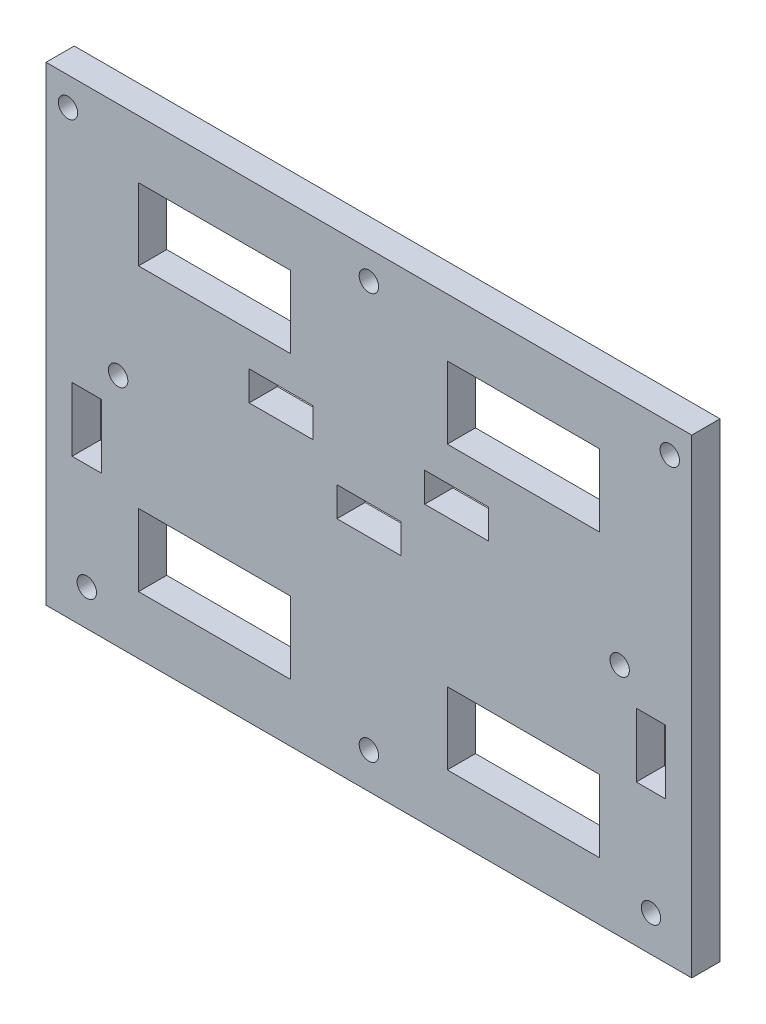
SolidWorks part; units mm, degrees
ref_plane "Front Plane" through (0, 0, 0) normal (0, 0, 1) x (1, 0, 0)
ref_plane "Top Plane" through (0, 0, 0) normal (0, 1, 0) x (1, 0, 0)
ref_plane "Right Plane" through (0, 0, 0) normal (1, 0, 0) x (0, 0, -1)
sketch "Sketch1" plane through (0, 0, 0) normal (0, 0, 1) x (1, 0, 0)
  line L0 (0, -37.5) -> (0, 37.5) construction
  line L1 (-51.5, -37.5) -> (51.5, -37.5)
  line L2 (-51.5, -37.5) -> (-51.5, 37.5)
  line L3 (-51.5, 37.5) -> (51.5, 37.5)
  line L4 (51.5, -37.5) -> (51.5, 37.5)
  line L5 (-51.5, -37.5) -> (51.5, 37.5) construction
  line L6 (-51.5, 37.5) -> (51.5, -37.5) construction
  line L7 (-51.5, 0) -> (51.5, 0) construction
  line L8 (-51.5, 22.5) -> (51.5, 22.5) construction
  line L9 (36.75, 16.75) -> (12.5, 28.25) construction
  line L10 (-36.75, 28.25) -> (-12.5, 28.25)
  line L11 (-36.75, 28.25) -> (-36.75, 16.75)
  line L12 (-36.75, 16.75) -> (-12.5, 16.75)
  line L13 (-12.5, 28.25) -> (-12.5, 16.75)
  line L14 (-36.75, 28.25) -> (-12.5, 16.75) construction
  line L15 (-36.75, 16.75) -> (-12.5, 28.25) construction
  line L16 (36.75, 28.25) -> (12.5, 16.75) construction
  line L17 (12.5, 28.25) -> (12.5, 16.75)
  line L18 (36.75, 16.75) -> (12.5, 16.75)
  line L19 (36.75, 28.25) -> (36.75, 16.75)
  line L20 (36.75, 28.25) -> (12.5, 28.25)
  line L21 (36.75, -28.25) -> (12.5, -16.75) construction
  line L22 (-36.75, -16.75) -> (-12.5, -28.25) construction
  line L23 (-36.75, -28.25) -> (-12.5, -16.75) construction
  line L24 (36.75, -16.75) -> (12.5, -28.25) construction
  line L25 (36.75, -28.25) -> (12.5, -28.25)
  line L26 (36.75, -28.25) -> (36.75, -16.75)
  line L27 (36.75, -16.75) -> (12.5, -16.75)
  line L28 (12.5, -28.25) -> (12.5, -16.75)
  line L29 (-12.5, -28.25) -> (-12.5, -16.75)
  line L30 (-36.75, -16.75) -> (-12.5, -16.75)
  line L31 (-36.75, -28.25) -> (-36.75, -16.75)
  line L32 (-36.75, -28.25) -> (-12.5, -28.25)
  point P0 (0, 0)
  point P12 (-24.625, 22.5)
  point P21 (24.625, 22.5)
  point P30 (24.625, -22.5)
  point P31 (-24.625, -22.5)
  dimension "D1" = 103
  dimension "D2" = 75
  dimension "D3" = 22.5
  dimension "D4" = 24.25
  dimension "D5" = 11.5
  dimension "D6" = 12.5
extrude "Boss-Extrude1" add sketch "Sketch1" along normal blind 4.5
sketch "Sketch2" plane through (0, 0, 4.5) normal (0, 0, 1) x (1, 0, 0)
  line L0 (0, -37.5) -> (0, 37.5) construction
  line L1 (-51.5, -37.5) -> (51.5, -37.5) construction
  line L2 (51.5, 37.5) -> (-51.5, 37.5) construction
  line L3 (-51.5, 0) -> (51.5, 0) construction
  line L4 (-51.5, 37.5) -> (-51.5, -37.5) construction
  line L5 (51.5, -37.5) -> (51.5, 37.5) construction
  line L6 (-40, 0) -> (40, 0) construction
  line L7 (-48, 33) -> (48, 33) construction
  circle A0 centre (-48, 33) radius 1.55
  circle A1 centre (48, 33) radius 1.55
  circle A2 centre (40, 0) radius 1.55
  circle A3 centre (-40, 0) radius 1.55
  circle A4 centre (0, 33) radius 1.55
  dimension "D1" = 3.1
  dimension "D7" = 3.1
  dimension "D8" = 3.1
  dimension "D9" = 3.1
  dimension "D2" = 48
  dimension "D3" = 33
  dimension "D4" = 80
  dimension "D5" = 40
  dimension "D6" = 0
extrude "screwHoles" cut sketch "Sketch2" against normal through all
sketch "Sketch3" plane through (0, 0, 4.5) normal (0, 0, 1) x (1, 0, 0)
  line L0 (-51.5, 9) -> (26.0486, 9) construction
  line L1 (-51.5, 37.5) -> (-51.5, -37.5) construction
  line L3 (0, 37.5) -> (0, -37.5) construction
  line L4 (51.5, 37.5) -> (-51.5, 37.5) construction
  line L5 (-51.5, -37.5) -> (51.5, -37.5) construction
  line L6 (19.1, 6.65) -> (8.9, 11.35) construction
  line L7 (-19.1, 11.35) -> (-8.9, 11.35)
  line L8 (-19.1, 11.35) -> (-19.1, 6.65)
  line L9 (-19.1, 6.65) -> (-8.9, 6.65)
  line L10 (-8.9, 11.35) -> (-8.9, 6.65)
  line L11 (-19.1, 11.35) -> (-8.9, 6.65) construction
  line L12 (-19.1, 6.65) -> (-8.9, 11.35) construction
  line L13 (19.1, 11.35) -> (8.9, 6.65) construction
  line L14 (8.9, 11.35) -> (8.9, 6.65)
  line L15 (19.1, 6.65) -> (8.9, 6.65)
  line L16 (19.1, 11.35) -> (19.1, 6.65)
  line L17 (19.1, 11.35) -> (8.9, 11.35)
  line L18 (-51.5, 37.5) -> (-51.5, -37.5) construction
  point P2 (-51.5, 0)
  point P12 (-14, 9)
  point P21 (14, 9)
  dimension "D1" = 10.2
  dimension "D2" = 4.7
  dimension "D3" = 14
  dimension "D4" = 9
extrude "BeltClamp" cut sketch "Sketch3" against normal through all
sketch "Sketch4" plane through (0, 0, 4.5) normal (0, 0, 1) x (1, 0, 0)
  line L0 (-51.5, 0) -> (51.5, 0) construction
  line L1 (-51.5, 37.5) -> (-51.5, -37.5) construction
  line L2 (51.5, -37.5) -> (51.5, 37.5) construction
  line L4 (-5.1, 2.35) -> (5.1, 2.35)
  line L5 (-5.1, 2.35) -> (-5.1, -2.35)
  line L6 (-5.1, -2.35) -> (5.1, -2.35)
  line L7 (5.1, 2.35) -> (5.1, -2.35)
  line L8 (-5.1, 2.35) -> (5.1, -2.35) construction
  line L9 (-5.1, -2.35) -> (5.1, 2.35) construction
  circle A0 centre (-40, 0) radius 1.55 construction
  point P6 (0, 0)
  dimension "D1" = 10.2
  dimension "D2" = 4.7
  dimension "D3" = 0
extrude "Cut-Extrude3" cut sketch "Sketch4" against normal through all
sketch "Sketch5" plane through (0, 0, 4.5) normal (0, 0, 1) x (1, 0, 0)
  line L0 (-51.5, -9.75) -> (51.5, -9.75) construction
  line L1 (-51.5, 37.5) -> (-51.5, -37.5) construction
  line L2 (51.5, -37.5) -> (51.5, 37.5) construction
  line L3 (5.1, -2.35) -> (5.1, 2.35) construction
  line L4 (0, -37.5) -> (0, 37.5) construction
  line L5 (-51.5, -37.5) -> (51.5, -37.5) construction
  line L6 (51.5, 37.5) -> (-51.5, 37.5) construction
  line L7 (-42.65, -14.85) -> (-47.35, -4.65) construction
  line L8 (42.65, -4.65) -> (47.35, -4.65)
  line L9 (42.65, -4.65) -> (42.65, -14.85)
  line L10 (42.65, -14.85) -> (47.35, -14.85)
  line L11 (47.35, -4.65) -> (47.35, -14.85)
  line L12 (42.65, -4.65) -> (47.35, -14.85) construction
  line L13 (42.65, -14.85) -> (47.35, -4.65) construction
  line L14 (-42.65, -4.65) -> (-47.35, -14.85) construction
  line L15 (-47.35, -4.65) -> (-47.35, -14.85)
  line L16 (-42.65, -14.85) -> (-47.35, -14.85)
  line L17 (-42.65, -4.65) -> (-42.65, -14.85)
  line L18 (-42.65, -4.65) -> (-47.35, -4.65)
  line L19 (45, -9.75) -> (45, -37.5) construction
  line L20 (-45, -9.75) -> (-45, -37.5) construction
  line L21 (-45, -31.75) -> (45, -31.75) construction
  circle A0 centre (45, -31.75) radius 1.55
  circle A1 centre (-45, -31.75) radius 1.55
  circle A2 centre (0, -31.75) radius 1.55
  point P6 (5.1, 0)
  point P15 (45, -9.75)
  point P24 (-45, -9.75)
  dimension "D7" = 3.1
  dimension "D5" = 3.1
  dimension "D1" = 9.75
  dimension "D2" = 10.2
  dimension "D3" = 4.7
  dimension "D4" = 45
  dimension "D6" = 22
extrude "Cut-Extrude4" cut sketch "Sketch5" against normal through all
sketch "Sketch6" plane through (0, 0, 4.5) normal (0, 0, 1) x (1, 0, 0)
  line L0 (-47.35, -9.75) -> (47.35, -9.75) construction
  line L1 (-47.35, -4.65) -> (-47.35, -14.85) construction
  line L2 (47.35, -14.85) -> (47.35, -4.65) construction
  line L3 (0, -2.35) -> (0, -37.5) construction
  line L4 (-5.1, -2.35) -> (5.1, -2.35) construction
  line L5 (-51.5, -37.5) -> (51.5, -37.5) construction
  line L6 (45, -14.85) -> (45, -4.65) construction
  line L7 (42.65, -14.85) -> (47.35, -14.85) construction
  line L8 (47.35, -4.65) -> (42.65, -4.65) construction
  line L9 (42.65, -4.65) -> (42.65, -14.85) construction
  line L10 (41.65, -15.85) -> (48.35, -15.85)
  line L11 (41.65, -15.85) -> (41.65, -3.65)
  line L12 (41.65, -3.65) -> (48.35, -3.65)
  line L13 (48.35, -15.85) -> (48.35, -3.65)
  line L14 (41.65, -15.85) -> (48.35, -3.65) construction
  line L15 (41.65, -3.65) -> (48.35, -15.85) construction
  line L16 (-41.65, -3.65) -> (-48.35, -15.85) construction
  line L17 (-41.65, -15.85) -> (-48.35, -3.65) construction
  line L18 (-45, -14.85) -> (-45, -4.65) construction
  line L19 (-48.35, -15.85) -> (-48.35, -3.65)
  line L20 (-41.65, -3.65) -> (-48.35, -3.65)
  line L21 (-41.65, -15.85) -> (-41.65, -3.65)
  line L22 (-41.65, -15.85) -> (-48.35, -15.85)
  circle A0 centre (45, -9.75) radius 1.55
  circle A1 centre (-45, -9.75) radius 1.55
  point P18 (45, -9.75)
  dimension "D3" = 3.1
  dimension "D1" = 1
  dimension "D2" = 1
extrude "FrontToRear1" [suppressed] add sketch "Sketch6" against normal up to surface (4.5 mm away) up to face at (1.55, -31.75, 0)
sketch "Sketch7" plane through (0, 0, 4.5) normal (0, 0, 1) x (1, 0, 0)
  line L0 (5.1, 2.35) -> (-5.1, 2.35) construction
  line L1 (-45, -3.35) -> (45, -3.35)
  line L2 (-45, -3.35) -> (-45, 3.35)
  line L3 (-45, 3.35) -> (45, 3.35)
  line L4 (45, -3.35) -> (45, 3.35)
  line L5 (-45, -3.35) -> (45, 3.35) construction
  line L6 (-45, 3.35) -> (45, -3.35) construction
  circle A0 centre (40, 0) radius 1.55 construction
  point P0 (0, 0)
  dimension "D1" = 1
  dimension "D2" = 5
extrude "FrontToRear2" [suppressed] add sketch "Sketch7" against normal through all
equation "\"X-ROD-SPACING\"=45"
equation "\"Y-ROD-SPACING\"=75"
equation "\"Z-ROD-SPACING\"=17.5"
equation "\"Y-BED-OFFSET\"=2"
equation "\"Y-BED-ROD-INSET\"=3.5"
equation "\"Y-BED-SCREW-SPACING\"=209"
equation "\"Y-BED-SCREW-CUTOUT-SLOT-HEIGHT\"=2"
equation "\"T-SLOT-NUT-FILLET-RADIUS\"=0.25"
equation "\"T-SLOT-SCREW-SHAFT-RADIUS\"=1.75"
equation "\"T-SLOT-SCREW-SHAFT-CUTOUT-LENGTH\"=10.5"
equation "\"T-SLOT-NUT-DEPTH\"=4.2"
equation "\"T-SLOT-NUT-WIDTH\"=3"
equation "\"T-SLOT-NUT-END-DISTANCE\"=8"
equation "\"ACRYLIC-THICKNESS\"=10"
equation "\"ACRYLIC-THICKNESS2\"=4.5"
equation "\"ACRYLIC-TAB-CUTOUT-SIZE\"=\"ACRYLIC-THICKNESS\"+\"ACRYLIC-TAB-TOLERANCE\"*2"
equation "\"ACRYLIC-TAB-WIDTH\"=\"ACRYLIC-THICKNESS\""
equation "\"ACRYLIC-M3-HOLE\"=3.1"
equation "\"SMOOTHROD-CAP-SCREW-DISTANCE\"=20"
equation "\"FRAME-WIDTH-INNER\"=370"
equation "\"NEMA17-HOLE-SPACING\"=31"
equation "\"NEMA17-CENTRAL-CUTOUT\"=22.5"
equation "\"Z-BRACKET-REACH\"=55"
equation "\"Z-ROD-INSET\"=16"
equation "\"TOP-BRACKET-SPACING\"=40"
equation "\"SMOOTHROD-X-LENGTH\"=350"
equation "\"SMOOTHROD-Y-LENGTH\"=350"
equation "\"SMOOTHROD-Z-LENGTH\"=350"
equation "\"SMOOTHROD-TIGHTENING-HEADROOM\"=.25"
equation "\"LEADSCREW-Z-LENGTH\"=300"
equation "\"SCREW-LENGTH-FRAME\"=\"ACRYLIC-THICKNESS\" + 10"
equation "\"SCREW-LENGTH-MOTOR\"=\"ACRYLIC-THICKNESS\" + 5"
equation "\"SCREW-HEAD-RADIUS\"=6"
equation "\"PRINTED-X-SMOOTHROD-DIAMETER\"=8.2"
equation "\"PRINTED-X-SMOOTHROD-CUTOUT\"=10"
equation "\"PRINTED-X-BASE-HEIGHT\"=10"
equation "\"PRINTED-LM8UU-CUTOUT-SIZE\"=15.25"
equation "\"PRINTED-LM8UU-CUTOUT-LENGTH\"=24.5"
equation "\"PRINTED-X-IDLER-HEIGHT\"=16"
equation "\"PSU-MOUNTING-WIDTH\"=95"
equation "\"PSU-MOUNTING-HEIGHT\"=177"
equation "\"Y-BELT-TO-ROD-DISTANCE\"=20"
equation "\"SPOOL-HOLDER-ROD-SPACING\"=150"
equation "\"D3@Sketch1\"=\"X-ROD-SPACING\"/2"
equation "\"D4@Sketch1\"=\"ACRYLIC-X-CARRIAGE-LM8UU-CUTOUT-WIDTH\""
equation "\"D1@Boss-Extrude1\"=\"ACRYLIC-THICKNESS2\""
equation "\"D1@Sketch2\"=\"ACRYLIC-M3-HOLE\""
equation "\"D1@Sketch3\"=\"ACRYLIC-TAB-CUTOUT-SIZE\""
equation "\"D2@Sketch3\"=\"ACRYLIC-THICKNESS2\"+\"ACRYLIC-TAB-TOLERANCE\"*2"
equation "\"ACRYLIC-X-CARRIAGE-WIDTH\"=55"
equation "\"ACRYLIC-X-CARRIAGE-HEIGHT\"=75"
equation "\"D2@Sketch1\"=\"ACRYLIC-X-CARRIAGE-HEIGHT\""
equation "\"ACRYLIC-X-CARRIAGE-CENTER-TAB-SPACING\"=14"
equation "\"D3@Sketch3\"=\"ACRYLIC-X-CARRIAGE-CENTER-TAB-SPACING\""
equation "\"SCREW-LENGTH-EXTRUDER\"=28"
equation "\"ACRYLIC-X-CARRIAGE-SCREW-SPACING-X\"=15"
equation "\"ACRYLIC-X-CARRIAGE-SCREW-SPACING-Y\"=33"
equation "\"D3@Sketch2\"=\"ACRYLIC-X-CARRIAGE-SCREW-SPACING-Y\""
equation "\"D1@Sketch4\"=\"ACRYLIC-TAB-CUTOUT-SIZE\""
equation "\"D2@Sketch4\"=\"ACRYLIC-THICKNESS2\"+\"ACRYLIC-TAB-TOLERANCE\"*2"
equation "\"D2@Sketch5\"=\"ACRYLIC-TAB-CUTOUT-SIZE\""
equation "\"D3@Sketch5\"=\"ACRYLIC-THICKNESS2\"+\"ACRYLIC-TAB-TOLERANCE\"*2"
equation "\"ACRYLIC-X-CARRIAGE-EXTRUDER-SHELF-DEPTH\"=\"ACRYLIC-X-CARRIAGE-EXTRUDER-OFFSET\" + 28"
equation "\"ACRYLIC-X-CARRIAGE-EXTRUDER-BRACE-SPACING\"=23"
equation "\"D4@Sketch5\"=\"ACRYLIC-X-CARRIAGE-DUAL-MOUNT-BRACE-WIDTH\""
equation "\"D1@Sketch5\"=\"ACRYLIC-THICKNESS2\"/2 + 7.5"
equation "\"D4@Sketch2\"=\"ACRYLIC-X-CARRIAGE-DUAL-MOUNT-SCREW-WIDTH\"*2"
equation "\"D5@Sketch2\"=\"ACRYLIC-X-CARRIAGE-DUAL-MOUNT-SCREW-WIDTH\""
equation "\"D7@Sketch2\"=\"ACRYLIC-M3-HOLE\""
equation "\"D8@Sketch2\"=\"ACRYLIC-M3-HOLE\""
equation "\"ACRYLIC-X-CARRIAGE-LM8UU-CUTOUT-WIDTH\"=24.25"
equation "\"ACRYLIC-TAB-TOLERANCE\"=.1"
equation "\"ACRYLIC-X-CARRIAGE-EXTRUDER-OFFSET\"=26"
equation "\"ACRYLIC-X-CARRIAGE-EXTRUDER-ANGLE\"=90"
equation "\"ACRYLIC-X-CARRIAGE-EXTRUDER-BRACE-TAB-OFFSET\"=20"
equation "\"ACRYLIC-X-CARRIAGE-EXTRUDER-BRACE-HEIGHT\"=35"
equation "\"ACRYLIC-X-CARRIAGE-EXTRUDER-BRACE-SCREW-SPACING\"=22"
equation "\"D5@Sketch5\"=\"ACRYLIC-M3-HOLE\""
equation "\"D3@Sketch6\"=\"ACRYLIC-M3-HOLE\""
equation "\"ACRYLIC-X-CARRIAGE-DUAL-WIDTH-MULTIPLIER\"=1.65"
equation "\"ACRYLIC-X-CARRIAGE-DUAL-HOTEND-SPACING\"=42"
equation "\"ACRYLIC-X-CARRIAGE-DUAL-WIDTH\"=103"
equation "\"ACRYLIC-X-CARRIAGE-DUAL-HOTEND-SEPARATION\"=35"
equation "\"ACRYLIC-X-CARRIAGE-DUAL-MOUNT-PLATE-DEPTH\"=76"
equation "\"ACRYLIC-X-CARRIAGE-DUAL-MOUNT-BRACE-WIDTH\"=45"
equation "\"ACRYLIC-X-CARRIAGE-DUAL-MOUNT-SCREW-WIDTH\"=40"
equation "\"D1@Sketch1\"=\"ACRYLIC-X-CARRIAGE-DUAL-WIDTH\""
equation "\"D9@Sketch2\"=\"ACRYLIC-M3-HOLE\""
equation "\"D7@Sketch5\"=\"ACRYLIC-M3-HOLE\""
equation "\"ACRYLIC-X-CARRIAGE-LM8UU-CUTOUT-HEIGHT\"=11.5"
equation "\"D5@Sketch1\"=\"ACRYLIC-X-CARRIAGE-LM8UU-CUTOUT-HEIGHT\""
